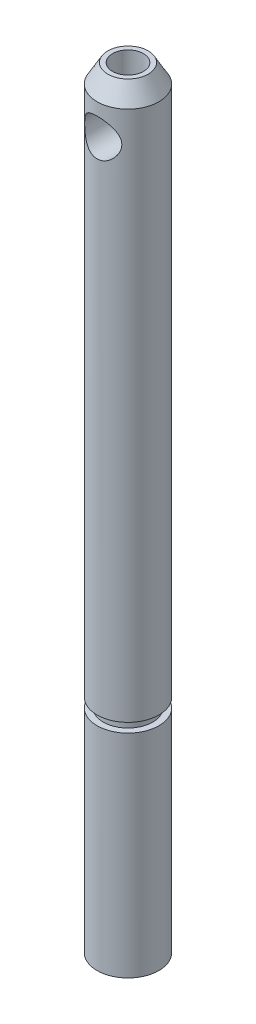
SolidWorks part; units mm, degrees
ref_plane "Front" through (0, 0, 0) normal (0, 0, 1) x (1, 0, 0)
ref_plane "Top" through (0, 0, 0) normal (0, 1, 0) x (1, 0, 0)
ref_plane "Right" through (0, 0, 0) normal (1, 0, 0) x (0, 0, -1)
sketch "Sketch3" plane through (0, 0, 0) normal (0, 1, 0) x (1, 0, 0)
  circle A0 centre (0, 0) radius 2.5
  dimension "D1" = 5
extrude "Boss-Extrude1" add sketch "Sketch3" along normal blind 62.3426
chamfer "Chamfer1" distance 1.5 angle 30 1 edges at (0, 62.3426, 2.5) first distance on face at (0, 62.3426, 2.5)
hole_wizard "M3x0.5 Tapped Hole1" positions "Sketch4" profile "Sketch5" tap size "M3x0.5" standard "ANSI Metric"
sketch "Sketch4" plane through (0, 62.3426, 0) normal (0, 1, 0) x (1, 0, 0)
  point P0 (0, 0)
cosmetic thread "Hole Thread1" parameters "D1"=4, "D2"=3
sketch "Sketch5" plane through (0, 62.3426, 0) normal (1, 0, 0) x (0, 0, 1)
  line L0 (0, 0) -> (0, 4.7511)
  line L1 (0, 4.7511) -> (1.25, 4)
  line L2 (1.25, 4) -> (1.25, 0)
  line L5 (1.25, 0) -> (0, 0)
  line L10 (0, 4.7511) -> (-1.25, 4) construction
  line L11 (0, -6.35) -> (0, 107.95) construction
  dimension "Tap Drill Dia." = 2.5
  dimension "Tap Drill Depth" = 4
  dimension "Drill Angle" = 118
cosmetic thread "Cosmetic Thread1" parameters "D1"=3.1708, "D2"=3
sketch "Sketch7" plane through (0, 0, 0) normal (0, 0, 1) x (1, 0, 0)
  line L0 (0, 62.3426) -> (0, 58.3426) construction
  line L1 (1.25, 62.3426) -> (-1.25, 62.3426) construction
  circle A0 centre (0, 58.3426) radius 1.5
  dimension "D2" = 3
  dimension "D1" = 4
extrude "Cut-Extrude1" cut sketch "Sketch7" against normal through all and the other way through all
sketch "Sketch8" plane through (0, 0, 0) normal (0, 0, 1) x (1, 0, 0)
  line L1 (-2.5, 0) -> (-1.5, 0)
  line L2 (-2.5, 0) -> (-2.5, 6)
  line L3 (-2.5, 6) -> (-1.5, 6)
  line L4 (-1.5, 0) -> (-1.5, 6)
  dimension "D1" = 6
  dimension "D2" = 1
extrude "Cut-Extrude2" cut sketch "Sketch8" against normal through all both and the other way through all
ref_plane "Plane1" through (0, 17.15, 0) normal (0, 1, 0) x (1, 0, 0)
sketch "Sketch9" plane through (0, 17.15, 0) normal (0, 1, 0) x (1, 0, 0)
  circle A0 centre (0, 0) radius 2
  circle A1 centre (0, 0) radius 3
  dimension "D1" = 4
  dimension "D2" = 6
extrude "Cut-Extrude3" cut sketch "Sketch9" along normal blind 0.75
